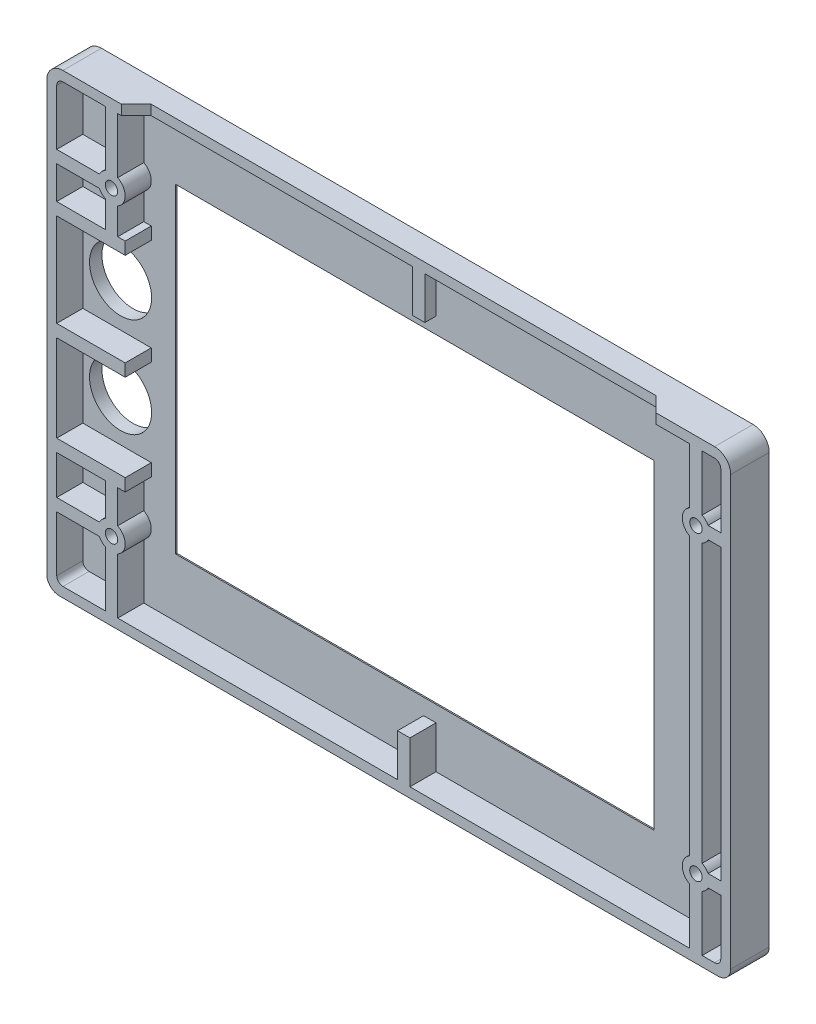
SolidWorks part; units mm, degrees
ref_plane "Спереди" through (0, 0, 0) normal (0, 0, 1) x (1, 0, 0)
ref_plane "Сверху" through (0, 0, 0) normal (0, 1, 0) x (1, 0, 0)
ref_plane "Справа" through (0, 0, 0) normal (1, 0, 0) x (0, 0, -1)
sketch "Эскиз1" plane through (0, 0, 0) normal (0, 0, 1) x (1, 0, 0)
  line L0 (-38.52, -25.78) -> (-38.52, 25.78)
  line L1 (38.52, -25.78) -> (-38.52, -25.78)
  line L2 (38.52, 25.78) -> (38.52, -25.78)
  line L3 (-38.52, 25.78) -> (38.52, 25.78)
  line L4 (50.46, 35.18) -> (50.46, 26.2296)
  line L5 (51.4196, 25.27) -> (53.46, 25.27)
  line L6 (53.46, 25.27) -> (53.46, 34.18)
  line L7 (52.46, 35.18) -> (50.46, 35.18)
  line L8 (50.46, 22.3104) -> (50.46, -22.3104)
  line L9 (51.4196, -23.27) -> (53.46, -23.27)
  line L10 (53.46, -23.27) -> (53.46, 23.27)
  line L11 (53.46, 23.27) -> (51.4196, 23.27)
  line L12 (50.46, -26.2296) -> (50.46, -35.18)
  line L13 (50.46, -35.18) -> (52.46, -35.18)
  line L14 (53.46, -34.18) -> (53.46, -25.27)
  line L15 (53.46, -25.27) -> (51.4196, -25.27)
  line L16 (-45.64, -22.3104) -> (-45.64, -17)
  line L17 (-45.64, -17) -> (-53.46, -17)
  line L18 (-53.46, -17) -> (-53.46, -23.27)
  line L19 (-53.46, -23.27) -> (-46.5996, -23.27)
  line L20 (1.41, -35.18) -> (1.41, -28.36)
  line L21 (1.41, -28.36) -> (3.41, -28.36)
  line L22 (3.41, -28.36) -> (3.41, -35.18)
  line L23 (3.41, -35.18) -> (48.46, -35.18)
  line L24 (48.46, -35.18) -> (48.46, -26.2296)
  line L25 (48.46, -22.3104) -> (48.46, 22.3104)
  line L26 (48.46, 26.2296) -> (48.46, 35.18)
  line L27 (48.46, 35.18) -> (3.41, 35.18)
  line L28 (3.41, 35.18) -> (3.41, 28.36)
  line L29 (3.41, 28.36) -> (1.41, 28.36)
  line L30 (1.41, 28.36) -> (1.41, 35.18)
  line L31 (1.41, 35.18) -> (-43.64, 35.18)
  line L32 (-43.64, 35.18) -> (-43.64, 26.2296)
  line L33 (-43.64, 22.3104) -> (-43.64, 18)
  line L34 (-43.64, 18) -> (-42.44, 18)
  line L35 (-42.44, 18) -> (-42.44, 16)
  line L36 (-42.44, 16) -> (-53.46, 16)
  line L37 (-53.46, 16) -> (-53.46, 1.0035)
  line L38 (-53.46, 1.0035) -> (-42.44, 1.0035)
  line L39 (-42.44, 1.0035) -> (-42.44, -0.9965)
  line L40 (-42.44, -0.9965) -> (-53.46, -0.9965)
  line L41 (-53.46, -0.9965) -> (-53.46, -15)
  line L42 (-53.46, -15) -> (-42.44, -15)
  line L43 (-42.44, -15) -> (-42.44, -17)
  line L44 (-42.44, -17) -> (-43.64, -17)
  line L45 (-43.64, -17) -> (-43.64, -22.3104)
  line L46 (-43.64, -26.2296) -> (-43.64, -35.18)
  line L47 (-43.64, -35.18) -> (1.41, -35.18)
  line L48 (-45.64, -35.18) -> (-45.64, -26.2296)
  line L49 (-46.5996, -25.27) -> (-53.46, -25.27)
  line L50 (-53.46, -25.27) -> (-53.46, -34.18)
  line L51 (-52.46, -35.18) -> (-45.64, -35.18)
  line L52 (-45.64, 18) -> (-45.64, 22.3104)
  line L53 (-46.5996, 23.27) -> (-53.46, 23.27)
  line L54 (-53.46, 23.27) -> (-53.46, 18)
  line L55 (-53.46, 18) -> (-45.64, 18)
  line L56 (-53.46, 25.27) -> (-46.5996, 25.27)
  line L57 (-45.64, 26.2296) -> (-45.64, 35.18)
  line L58 (-45.64, 35.18) -> (-52.46, 35.18)
  line L59 (-53.46, 34.18) -> (-53.46, 25.27)
  line L60 (55.06, -34.78) -> (55.06, 34.18)
  line L61 (40.66, 36.78) -> (43.06, 36.78)
  line L62 (40.66, 36.78) -> (-40.66, 36.78)
  line L63 (40.66, 35.18) -> (40.66, 36.78)
  line L64 (43.06, 35.18) -> (43.06, 36.78)
  line L65 (52.46, 36.78) -> (43.06, 36.78)
  line L66 (-53.06, -36.78) -> (53.06, -36.78)
  line L67 (-55.06, 34.18) -> (-55.06, -34.78)
  line L68 (-40.66, 36.78) -> (-40.66, 35.18)
  line L69 (-43.06, 35.18) -> (-43.06, 36.78)
  line L70 (-43.06, 36.78) -> (-40.66, 36.78)
  line L71 (-43.06, 36.78) -> (-52.46, 36.78)
  line L72 (9.4479, -31.9824) -> (8.7918, -31.9824)
  line L73 (10.3836, -30.0436) -> (10.3836, -34.7998)
  line L74 (9.4479, -30.6181) -> (9.4479, -31.9824)
  line L75 (9.4479, -32.6528) -> (9.4479, -34.2212)
  line L76 (8.6152, -32.6528) -> (9.4479, -32.6528)
  line L77 (4.3458, -34.8886) -> (5.2897, -34.8886)
  line L78 (5.2897, -34.8886) -> (5.2897, -29.961)
  line L79 (5.2897, -29.961) -> (4.3458, -29.961)
  line L80 (4.3458, -29.961) -> (4.3458, -34.8886)
  line L81 (2.357, -34.8886) -> (3.2805, -34.8886)
  line L82 (-0.0297, -34.2243) -> (0.7152, -34.2243)
  line L83 (-2.6022, -34.8886) -> (-1.6767, -34.8886)
  line L84 (-1.3889, -29.961) -> (-2.2012, -29.961)
  line L85 (2.8805, -29.961) -> (2.0805, -29.961)
  line L86 (-4.44, -32.5967) -> (-4.69, -32.5967)
  line L87 (-4.44, -31.9406) -> (-4.44, -32.5967)
  line L88 (-4.7594, -31.9406) -> (-4.44, -31.9406)
  line L89 (-3.5849, -30.2661) -> (-3.9104, -30.8457)
  line L90 (-3.6441, -34.0518) -> (-3.4839, -34.7161)
  line L91 (-8.0523, -34.8886) -> (-11.4727, -34.8886)
  line L92 (-11.4727, -34.8886) -> (-11.4727, -34.211)
  line L93 (-11.4727, -34.211) -> (-9.0145, -34.211)
  line L94 (-7.9329, -30.4844) -> (-8.3553, -31.012)
  arc A0 (51.4196, 25.27) -> (50.46, 26.2296) centre (49.46, 24.27) ccw
  arc A1 (53.46, 34.18) -> (52.46, 35.18) centre (52.46, 34.18) ccw
  arc A2 (48.46, -22.3104) -> (48.46, -26.2296) centre (49.46, -24.27) ccw
  arc A3 (48.46, 26.2296) -> (48.46, 22.3104) centre (49.46, 24.27) ccw
  arc A4 (-43.64, 22.3104) -> (-43.64, 26.2296) centre (-44.64, 24.27) ccw
  arc A5 (-43.64, -26.2296) -> (-43.64, -22.3104) centre (-44.64, -24.27) ccw
  arc A6 (51.4196, -23.27) -> (50.46, -22.3104) centre (49.46, -24.27) ccw
  arc A7 (50.46, 22.3104) -> (51.4196, 23.27) centre (49.46, 24.27) ccw
  circle A8 centre (49.46, 24.27) radius 1
  arc A9 (52.46, -35.18) -> (53.46, -34.18) centre (52.46, -34.18) ccw
  arc A10 (50.46, -26.2296) -> (51.4196, -25.27) centre (49.46, -24.27) ccw
  circle A11 centre (49.46, -24.27) radius 1
  circle A12 centre (-44.64, -24.27) radius 1
  circle A13 centre (-47.385, -8) radius 5
  arc A14 (-45.64, -22.3104) -> (-46.5996, -23.27) centre (-44.64, -24.27) ccw
  arc A15 (-46.5996, -25.27) -> (-45.64, -26.2296) centre (-44.64, -24.27) ccw
  arc A16 (-53.46, -34.18) -> (-52.46, -35.18) centre (-52.46, -34.18) ccw
  arc A17 (-46.5996, 23.27) -> (-45.64, 22.3104) centre (-44.64, 24.27) ccw
  arc A18 (-45.64, 26.2296) -> (-46.5996, 25.27) centre (-44.64, 24.27) ccw
  arc A19 (-52.46, 35.18) -> (-53.46, 34.18) centre (-52.46, 34.18) ccw
  circle A20 centre (-44.64, 24.27) radius 1
  arc A21 (55.06, 34.18) -> (52.46, 36.78) centre (52.46, 34.18) ccw
  arc A22 (53.06, -36.78) -> (55.06, -34.78) centre (53.06, -34.78) ccw
  arc A23 (-55.06, -34.78) -> (-53.06, -36.78) centre (-53.06, -34.78) ccw
  arc A24 (-52.46, 36.78) -> (-55.06, 34.18) centre (-52.46, 34.18) ccw
  circle A25 centre (-47.385, 8) radius 5
  spline S0 degree 3 poles (8.8387, -30.6038) (8.8833, -30.6036) (8.9673, -30.6032) (9.0853, -30.6059) (9.1881, -30.6074) (9.2745, -30.6106) (9.3438, -30.6137) (9.3948, -30.6162) (9.4275, -30.6165) (9.4431, -30.6177) (9.4479, -30.6181) knots 0 0 0 0 0.21934 0.413593 0.581062 0.725143 0.83911 0.922894 0.976499 1 1 1 1
  spline S1 degree 3 poles (8.7918, -31.9824) (8.703, -31.9808) (8.5318, -31.9778) (8.3224, -31.9585) (8.1673, -31.9307) (8.0608, -31.9062) (7.9634, -31.873) (7.8743, -31.8348) (7.7941, -31.7893) (7.7221, -31.7393) (7.6618, -31.6806) (7.6079, -31.6186) (7.567, -31.5468) (7.537, -31.4674) (7.5197, -31.3791) (7.5174, -31.3175) (7.5163, -31.2855) knots 0 0 0 0 0.163347 0.314852 0.386023 0.452934 0.515643 0.575031 0.631053 0.684865 0.735751 0.78549 0.835382 0.886853 0.941078 1 1 1 1
  spline S2 degree 3 poles (7.5163, -31.2855) (7.5173, -31.2558) (7.5194, -31.1981) (7.5385, -31.1159) (7.5677, -31.0403) (7.612, -30.9738) (7.6659, -30.9129) (7.7295, -30.8575) (7.804, -30.8086) (7.888, -30.765) (7.981, -30.726) (8.0841, -30.694) (8.1957, -30.6651) (8.3586, -30.636) (8.5736, -30.6092) (8.7492, -30.6057) (8.8387, -30.6038) knots 0 0 0 0 0.05392 0.104621 0.152614 0.200464 0.24909 0.299926 0.35343 0.410679 0.471653 0.536572 0.606754 0.680971 0.837269 1 1 1 1
  spline S3 degree 3 poles (6.5499, -31.2375) (6.5503, -31.2702) (6.551, -31.3344) (6.5632, -31.4285) (6.58, -31.5187) (6.6048, -31.6051) (6.6363, -31.6873) (6.6743, -31.7662) (6.7201, -31.8401) (6.7893, -31.9319) (6.8856, -32.0339) (7.0163, -32.1333) (7.1586, -32.2105) (7.2615, -32.24) (7.3132, -32.2549) knots 0 0 0 0 0.071306 0.140095 0.206635 0.271494 0.335883 0.398637 0.462303 0.525409 0.649341 0.766942 0.882847 1 1 1 1
  spline S4 degree 3 poles (8.8846, -29.912) (8.8067, -29.9128) (8.6525, -29.9144) (8.424, -29.9264) (8.2016, -29.9485) (7.9858, -29.976) (7.7792, -30.0137) (7.5847, -30.0653) (7.4024, -30.1263) (7.2348, -30.2026) (7.0811, -30.288) (6.9451, -30.3875) (6.8276, -30.4998) (6.7277, -30.6234) (6.648, -30.7597) (6.5904, -30.9079) (6.5558, -31.0689) (6.5519, -31.1802) (6.5499, -31.2375) knots 0 0 0 0 0.077891 0.154178 0.22866 0.301383 0.371619 0.438435 0.502425 0.563614 0.622247 0.677955 0.731594 0.784335 0.836305 0.88885 0.942744 1 1 1 1
  spline S5 degree 3 poles (8.8846, -29.912) (8.9411, -29.9124) (9.0578, -29.9132) (9.2367, -29.9199) (9.4225, -29.9289) (9.6109, -29.9411) (9.7995, -29.9561) (9.9887, -29.9757) (10.1841, -30.001) (10.3154, -30.029) (10.3836, -30.0436) knots 0 0 0 0 0.112395 0.232298 0.356344 0.482533 0.608194 0.732756 0.861249 1 1 1 1
  spline S6 degree 3 poles (9.4479, -34.2212) (9.4476, -34.2212) (9.4338, -34.2216) (9.415, -34.224) (9.3881, -34.2254) (9.3714, -34.2263) knots 0.196755 0.196755 0.196755 0.196755 0.204403 0.505519 1 1 1 1
  spline S7 degree 3 poles (9.3714, -34.2263) (9.3357, -34.228) (9.2588, -34.2317) (9.1337, -34.2376) (8.9891, -34.2389) (8.8857, -34.2387) (8.8306, -34.2386) knots 0 0 0 0 0.198249 0.426644 0.694476 1 1 1 1
  spline S8 degree 3 poles (8.8306, -34.2386) (8.7237, -34.2369) (8.5167, -34.2337) (8.2634, -34.2103) (8.074, -34.1825) (7.9439, -34.1541) (7.8241, -34.118) (7.7132, -34.077) (7.6129, -34.027) (7.5227, -33.9689) (7.4453, -33.9005) (7.376, -33.8262) (7.3216, -33.7401) (7.281, -33.6446) (7.2588, -33.5378) (7.2556, -33.4638) (7.254, -33.4253) knots 0 0 0 0 0.161567 0.312905 0.384192 0.451081 0.513893 0.573309 0.629663 0.683159 0.73493 0.785547 0.836198 0.888066 0.941735 1 1 1 1
  spline S9 degree 3 poles (7.254, -33.4253) (7.2553, -33.3905) (7.2578, -33.3237) (7.2734, -33.2271) (7.3036, -33.1402) (7.3437, -33.0608) (7.3957, -32.9905) (7.4561, -32.9254) (7.53, -32.8714) (7.6121, -32.8213) (7.7058, -32.7802) (7.8092, -32.7445) (7.9232, -32.7149) (8.0471, -32.6924) (8.1795, -32.6737) (8.3192, -32.6625) (8.4651, -32.6533) (8.5645, -32.653) (8.6152, -32.6528) knots 0 0 0 0 0.059005 0.1135 0.165365 0.214695 0.263903 0.313328 0.36484 0.418717 0.476355 0.538084 0.604336 0.67603 0.75182 0.831238 0.913947 1 1 1 1
  spline S10 degree 3 poles (2.1643, -31.3785) (2.1695, -31.4485) (2.1846, -31.6569) (2.2076, -32.0116) (2.2354, -32.4511) (2.2627, -32.9123) (2.2892, -33.3905) (2.3138, -33.881) (2.336, -34.3814) (2.35, -34.7185) (2.357, -34.8886) knots 0.048777 0.048777 0.048777 0.048777 0.105755 0.218376 0.337335 0.463184 0.593427 0.726123 0.861826 1 1 1 1
  spline S11 degree 3 poles (0.7152, -34.2243) (0.7316, -34.1896) (0.7654, -34.1179) (0.8168, -34.0059) (0.8756, -33.8887) (0.9365, -33.7635) (1.0024, -33.6325) (1.0688, -33.4933) (1.1414, -33.3486) (1.2379, -33.145) (1.363, -32.8883) (1.523, -32.5878) (1.6796, -32.2946) (1.8056, -32.0564) (1.9019, -31.873) (1.9703, -31.7439) (2.0387, -31.6232) (2.0923, -31.5275) (2.1326, -31.4564) (2.1508, -31.4127) (2.1611, -31.3874) (2.1643, -31.3785) knots 0 0 0 0 0.034001 0.070298 0.109281 0.150287 0.193721 0.239316 0.287067 0.337251 0.439092 0.540278 0.639048 0.733898 0.779229 0.82268 0.863459 0.902218 0.920031 0.935833 0.944187 0.944187 0.944187 0.944187
  spline S12 degree 3 poles (-0.0297, -34.2243) (-0.046, -34.1896) (-0.0798, -34.1177) (-0.1329, -34.0065) (-0.1898, -33.8883) (-0.2513, -33.7636) (-0.3167, -33.6322) (-0.3847, -33.4936) (-0.4568, -33.3483) (-0.5548, -33.1448) (-0.6838, -32.8899) (-0.8396, -32.5863) (-0.9975, -32.2899) (-1.1245, -32.0457) (-1.2245, -31.8571) (-1.295, -31.724) (-1.3641, -31.5999) (-1.4189, -31.5027) (-1.4589, -31.431) (-1.4749, -31.3951) (-1.482, -31.3773) (-1.4826, -31.3758) knots 0.056566 0.056566 0.056566 0.056566 0.090499 0.126852 0.165626 0.206551 0.249898 0.295535 0.34319 0.393406 0.495447 0.596014 0.695386 0.792598 0.839592 0.884302 0.925936 0.96529 0.983067 0.998563 1 1 1 1
  spline S13 degree 3 poles (-1.6767, -34.8886) (-1.6696, -34.7185) (-1.6557, -34.3817) (-1.6334, -33.8814) (-1.609, -33.3912) (-1.5824, -32.9133) (-1.5549, -32.4528) (-1.5277, -32.0136) (-1.5031, -31.6574) (-1.4878, -31.4474) (-1.4826, -31.3758) knots 0 0 0 0 0.138171 0.273597 0.406566 0.536531 0.662102 0.781058 0.893696 0.951951 0.951951 0.951951 0.951951
  spline S14 degree 3 poles (-2.2012, -29.961) (-2.2443, -30.3612) (-2.3312, -31.1678) (-2.4392, -32.3895) (-2.5321, -33.6318) (-2.5787, -34.4674) (-2.6022, -34.8886) knots 0 0 0 0 0.244221 0.492231 0.74407 1 1 1 1
  spline S15 degree 3 poles (-1.3889, -29.961) (-1.3506, -30.0179) (-1.2719, -30.1348) (-1.1563, -30.3176) (-1.0373, -30.5103) (-0.8772, -30.7858) (-0.674, -31.1485) (-0.4367, -31.5996) (-0.2042, -32.056) (-0.0123, -32.4281) (0.126, -32.7152) (0.2145, -32.9151) (0.2867, -33.1027) (0.3246, -33.2251) (0.3427, -33.2834) knots 0 0 0 0 0.054878 0.112558 0.17283 0.235807 0.367222 0.504974 0.643062 0.776526 0.839498 0.897672 0.951178 1 1 1 1
  spline S16 degree 3 poles (0.3427, -33.2834) (0.3608, -33.2251) (0.3986, -33.1027) (0.4713, -32.9156) (0.5567, -32.7151) (0.6947, -32.4303) (0.8804, -32.0602) (1.1142, -31.6125) (1.3498, -31.1692) (1.5891, -30.7445) (1.8271, -30.3408) (1.997, -30.0861) (2.0805, -29.961) knots 0 0 0 0 0.04878 0.102241 0.160149 0.222705 0.354839 0.490754 0.625976 0.755591 0.879939 1 1 1 1
  spline S17 degree 3 poles (2.8805, -29.961) (2.9049, -30.1534) (2.9537, -30.539) (3.0172, -31.1217) (3.0712, -31.7142) (3.1238, -32.3189) (3.1704, -32.937) (3.2125, -33.569) (3.2495, -34.2207) (3.27, -34.6627) (3.2805, -34.8886) knots 0 0 0 0 0.11768 0.235785 0.355571 0.478591 0.603995 0.73159 0.862829 1 1 1 1
  spline S18 degree 3 poles (-4.7594, -31.9406) (-4.8227, -31.9389) (-4.9516, -31.9356) (-5.1121, -31.9145) (-5.239, -31.8877) (-5.3305, -31.8629) (-5.416, -31.8294) (-5.4977, -31.7927) (-5.5717, -31.7458) (-5.6413, -31.6949) (-5.7, -31.6329) (-5.7547, -31.5671) (-5.7979, -31.4906) (-5.8283, -31.405) (-5.8472, -31.3104) (-5.8492, -31.2444) (-5.8502, -31.21) knots 0 0 0 0 0.128599 0.261659 0.328043 0.3919 0.453991 0.514249 0.573485 0.631648 0.688797 0.746296 0.805071 0.866034 0.930111 1 1 1 1
  spline S19 degree 3 poles (-5.8502, -31.21) (-5.8496, -31.1817) (-5.8483, -31.1268) (-5.8346, -31.048) (-5.8136, -30.9753) (-5.7822, -30.9096) (-5.7444, -30.8496) (-5.7012, -30.7943) (-5.6508, -30.7457) (-5.5955, -30.7017) (-5.535, -30.6623) (-5.4686, -30.6302) (-5.3976, -30.6032) (-5.2952, -30.5766) (-5.1594, -30.5526) (-5.0479, -30.5494) (-4.991, -30.5477) knots 0 0 0 0 0.069224 0.134278 0.19516 0.254043 0.312059 0.368394 0.425536 0.483041 0.541504 0.60186 0.663286 0.727145 0.860677 1 1 1 1
  spline S20 degree 3 poles (-4.991, -30.5477) (-4.9369, -30.5485) (-4.8331, -30.55) (-4.6837, -30.5669) (-4.5469, -30.5929) (-4.3789, -30.6487) (-4.1685, -30.7341) (-3.9994, -30.8072) (-3.9104, -30.8457) knots 0 0 0 0 0.143407 0.274916 0.398142 0.511615 0.743135 1 1 1 1
  spline S21 degree 3 poles (-6.0808, -33.46) (-6.0796, -33.4211) (-6.0773, -33.346) (-6.0549, -33.2387) (-6.0209, -33.1398) (-5.9697, -33.0519) (-5.9079, -32.9729) (-5.8365, -32.9017) (-5.756, -32.8382) (-5.6649, -32.7843) (-5.5654, -32.7372) (-5.457, -32.6978) (-5.3397, -32.6648) (-5.1717, -32.6323) (-4.9542, -32.6031) (-4.7782, -32.5988) (-4.69, -32.5967) knots 0 0 0 0 0.063414 0.122322 0.178344 0.233299 0.287497 0.341676 0.397433 0.454469 0.514074 0.576784 0.642525 0.712758 0.856069 1 1 1 1
  spline S22 degree 3 poles (-4.8675, -34.2875) (-4.9206, -34.2872) (-5.0232, -34.2865) (-5.1706, -34.2747) (-5.3064, -34.258) (-5.4299, -34.2337) (-5.5418, -34.2026) (-5.6412, -34.1633) (-5.7301, -34.1196) (-5.8055, -34.0653) (-5.8699, -34.0055) (-5.9268, -33.9419) (-5.9748, -33.8735) (-6.0143, -33.8003) (-6.0438, -33.7219) (-6.065, -33.6388) (-6.0788, -33.5509) (-6.0802, -33.4906) (-6.0808, -33.46) knots 0 0 0 0 0.095454 0.184416 0.265837 0.341304 0.410631 0.474364 0.533463 0.588294 0.640682 0.691385 0.741454 0.790719 0.840484 0.891676 0.944886 1 1 1 1
  spline S23 degree 3 poles (-4.8675, -34.2875) (-4.8015, -34.2868) (-4.6743, -34.2852) (-4.4914, -34.2683) (-4.3236, -34.2431) (-4.126, -34.1931) (-3.9029, -34.1232) (-3.7275, -34.0748) (-3.6441, -34.0518) knots 0 0 0 0 0.158157 0.304619 0.439944 0.564077 0.792564 1 1 1 1
  spline S24 degree 3 poles (-3.4839, -34.7161) (-3.5214, -34.7331) (-3.6011, -34.7692) (-3.7343, -34.8131) (-3.8879, -34.8545) (-4.062, -34.8961) (-4.2545, -34.9346) (-4.46, -34.9659) (-4.6708, -34.9885) (-4.8127, -34.9913) (-4.8828, -34.9926) knots 0 0 0 0 0.086022 0.182972 0.292897 0.41867 0.557194 0.703264 0.853385 1 1 1 1
  spline S25 degree 3 poles (-4.8828, -34.9926) (-4.9713, -34.9915) (-5.1425, -34.9892) (-5.39, -34.9661) (-5.6194, -34.9306) (-5.8309, -34.8782) (-6.0247, -34.8127) (-6.2028, -34.7377) (-6.3636, -34.6499) (-6.5073, -34.5507) (-6.6333, -34.4415) (-6.7413, -34.3233) (-6.8324, -34.1976) (-6.9029, -34.0623) (-6.9563, -33.9211) (-6.9973, -33.7759) (-7.0195, -33.6256) (-7.0229, -33.5243) (-7.0247, -33.4732) knots 0 0 0 0 0.089962 0.17401 0.252482 0.325884 0.39523 0.460312 0.522228 0.581139 0.637527 0.691389 0.743699 0.794911 0.846042 0.896975 0.948044 1 1 1 1
  spline S26 degree 3 poles (-7.0247, -33.4732) (-7.0233, -33.4317) (-7.0207, -33.35) (-7.005, -33.2296) (-6.9744, -33.1152) (-6.935, -33.0052) (-6.8838, -32.9015) (-6.8279, -32.8011) (-6.761, -32.708) (-6.6895, -32.6191) (-6.6091, -32.5369) (-6.5217, -32.4617) (-6.4269, -32.3936) (-6.3271, -32.3351) (-6.2277, -32.2865) (-6.1352, -32.2461) (-6.0492, -32.2213) (-5.9942, -32.2129) (-5.9686, -32.2089) knots 0 0 0 0 0.06994 0.137555 0.2038 0.269009 0.333802 0.39843 0.462131 0.526429 0.590405 0.655367 0.720198 0.78668 0.849929 0.906394 0.956416 1 1 1 1
  spline S27 degree 3 poles (-5.9686, -32.2089) (-6.0196, -32.1923) (-6.1231, -32.1585) (-6.2678, -32.0749) (-6.4056, -31.9685) (-6.5121, -31.862) (-6.5918, -31.768) (-6.6429, -31.6915) (-6.6869, -31.6127) (-6.7243, -31.5312) (-6.7515, -31.4461) (-6.7709, -31.3583) (-6.7837, -31.2678) (-6.7852, -31.2063) (-6.7859, -31.1753) knots 0 0 0 0 0.114054 0.231061 0.353418 0.483956 0.550788 0.615443 0.67929 0.7428 0.805987 0.869042 0.934057 1 1 1 1
  spline S28 degree 3 poles (-6.7859, -31.1753) (-6.785, -31.131) (-6.7831, -31.0432) (-6.7612, -30.9138) (-6.7289, -30.7875) (-6.6828, -30.665) (-6.6242, -30.5472) (-6.5493, -30.4371) (-6.4612, -30.3336) (-6.3585, -30.2374) (-6.2417, -30.1491) (-6.1092, -30.0713) (-5.9614, -30.0056) (-5.7996, -29.9494) (-5.6232, -29.9045) (-5.4325, -29.8724) (-5.2275, -29.8527) (-5.0863, -29.8508) (-5.0135, -29.8497) knots 0 0 0 0 0.05332 0.105591 0.157665 0.210174 0.262946 0.315787 0.370138 0.426369 0.484878 0.546222 0.610954 0.6795 0.752241 0.829972 0.912285 1 1 1 1
  spline S29 degree 3 poles (-5.0135, -29.8497) (-4.9395, -29.8516) (-4.7927, -29.8552) (-4.5781, -29.8879) (-4.3754, -29.9314) (-4.1881, -29.9823) (-4.0174, -30.0393) (-3.8617, -30.104) (-3.7172, -30.1775) (-3.6289, -30.2366) (-3.5849, -30.2661) knots 0 0 0 0 0.147019 0.291928 0.431041 0.559433 0.678001 0.788734 0.894679 1 1 1 1
  spline S30 degree 3 poles (-8.0523, -34.8886) (-8.0471, -34.8597) (-8.0384, -34.8117) (-8.032, -34.7489) (-8.033, -34.7028) (-8.0329, -34.6763) (-8.0329, -34.6641) knots 0 0 0 0 0.389156 0.647639 0.837372 1 1 1 1
  spline S31 degree 3 poles (-9.0145, -34.211) (-9.0161, -34.2003) (-9.02, -34.1737) (-9.0429, -34.1299) (-9.0736, -34.0721) (-9.1351, -33.9754) (-9.2285, -33.8431) (-9.3622, -33.6846) (-9.5109, -33.5278) (-9.6665, -33.3764) (-9.8197, -33.2379) (-9.9183, -33.1488) (-9.9645, -33.1069) knots 0 0 0 0 0.021915 0.054543 0.099576 0.156004 0.28792 0.429836 0.578605 0.728794 0.872731 1 1 1 1
  spline S32 degree 3 poles (-9.388, -32.5804) (-9.3098, -32.6515) (-9.151, -32.796) (-8.9109, -33.0129) (-8.6807, -33.2425) (-8.5065, -33.4478) (-8.382, -33.6201) (-8.2963, -33.753) (-8.2215, -33.8918) (-8.1543, -34.0346) (-8.0994, -34.183) (-8.0605, -34.3379) (-8.038, -34.4991) (-8.0346, -34.6086) (-8.0329, -34.6641) knots 0 0 0 0 0.123482 0.250869 0.377863 0.503065 0.564821 0.626105 0.687624 0.748955 0.810296 0.872165 0.935156 1 1 1 1
  spline S33 degree 3 poles (-9.4931, -30.5548) (-9.4306, -30.5568) (-9.3088, -30.5607) (-9.1353, -30.6011) (-8.978, -30.6552) (-8.8358, -30.718) (-8.7069, -30.7879) (-8.5939, -30.8717) (-8.4816, -30.9541) (-8.3976, -30.9926) (-8.3553, -31.012) knots 0 0 0 0 0.150082 0.29246 0.426517 0.549992 0.666122 0.778285 0.888375 1 1 1 1
  spline S34 degree 3 poles (-9.4931, -30.5548) (-9.5497, -30.5566) (-9.6605, -30.5599) (-9.7953, -30.588) (-9.8965, -30.6184) (-9.9665, -30.6484) (-10.0313, -30.6841) (-10.0905, -30.7263) (-10.1452, -30.7731) (-10.1931, -30.8265) (-10.2352, -30.885) (-10.2715, -30.9492) (-10.3011, -31.0196) (-10.3229, -31.0973) (-10.3348, -31.1824) (-10.3362, -31.2416) (-10.337, -31.2722) knots 0 0 0 0 0.135399 0.264894 0.327986 0.388175 0.446853 0.504682 0.56182 0.618888 0.676055 0.734022 0.79496 0.858372 0.926652 1 1 1 1
  spline S35 degree 3 poles (-9.388, -32.5804) (-9.4501, -32.5261) (-9.5717, -32.4198) (-9.7479, -32.2605) (-9.9083, -32.1019) (-10.0513, -31.9437) (-10.1705, -31.7832) (-10.2493, -31.6444) (-10.2956, -31.5317) (-10.3188, -31.4463) (-10.3339, -31.3598) (-10.336, -31.3015) (-10.337, -31.2722) knots 0 0 0 0 0.148632 0.291468 0.428085 0.555373 0.675595 0.787891 0.842105 0.894931 0.947163 1 1 1 1
  spline S36 degree 3 poles (-11.2962, -31.2508) (-11.2948, -31.292) (-11.292, -31.3747) (-11.2699, -31.4982) (-11.2325, -31.62) (-11.1821, -31.7402) (-11.1207, -31.8588) (-11.0481, -31.9749) (-10.9693, -32.0919) (-10.8459, -32.2463) (-10.6732, -32.4413) (-10.4436, -32.6681) (-10.204, -32.89) (-10.0432, -33.0356) (-9.9645, -33.1069) knots 0 0 0 0 0.052684 0.105639 0.159681 0.21522 0.271989 0.330139 0.390182 0.452096 0.582665 0.722824 0.864298 1 1 1 1
  spline S37 degree 3 poles (-11.2962, -31.2508) (-11.2949, -31.1983) (-11.2923, -31.0957) (-11.2704, -30.9458) (-11.2348, -30.8047) (-11.1857, -30.6711) (-11.1209, -30.5468) (-11.0433, -30.4298) (-10.9487, -30.3238) (-10.8429, -30.2241) (-10.7218, -30.135) (-10.5863, -30.0584) (-10.4368, -29.9945) (-10.2741, -29.9395) (-10.096, -29.9002) (-9.9048, -29.8704) (-9.6995, -29.8532) (-9.5581, -29.8509) (-9.4849, -29.8497) knots 0 0 0 0 0.060615 0.118612 0.174591 0.228711 0.282699 0.336244 0.390581 0.446499 0.504143 0.563838 0.626 0.6919 0.762101 0.836507 0.91543 1 1 1 1
  spline S38 degree 3 poles (-7.9329, -30.4844) (-7.9663, -30.4471) (-8.0371, -30.3678) (-8.1705, -30.2625) (-8.3296, -30.1617) (-8.5139, -30.0652) (-8.7245, -29.9798) (-8.9172, -29.922) (-9.0823, -29.8833) (-9.2131, -29.8651) (-9.3476, -29.8519) (-9.4386, -29.8505) (-9.4849, -29.8497) knots 0 0 0 0 0.087147 0.184828 0.294576 0.414848 0.54661 0.689569 0.764861 0.841503 0.919416 1 1 1 1
sketch "Эскиз2" plane through (0, 0, 0) normal (0, 0, 1) x (1, 0, 0)
  line L0 (-55.06, 34.18) -> (-55.06, -34.78) construction
  line L1 (-43.06, 36.78) -> (-52.46, 36.78) construction
  line L2 (-43.06, 36.78) -> (-40.66, 36.78) construction
  line L3 (38.52, 25.78) -> (38.52, -25.78) construction
  line L4 (-38.52, 25.78) -> (38.52, 25.78) construction
  line L5 (55.06, -34.78) -> (55.06, 34.18) construction
  line L6 (52.46, 36.78) -> (43.06, 36.78) construction
  line L7 (40.66, 36.78) -> (43.06, 36.78) construction
  line L8 (40.66, 36.78) -> (-40.66, 36.78) construction
  line L9 (-55.06, 34.18) -> (-55.06, -34.78)
  line L10 (-43.06, 36.78) -> (-52.46, 36.78)
  line L11 (-43.06, 36.78) -> (-40.66, 36.78)
  line L12 (38.52, 25.78) -> (38.52, -25.78)
  line L13 (-38.52, 25.78) -> (38.52, 25.78)
  line L14 (55.06, -34.78) -> (55.06, 34.18)
  line L15 (52.46, 36.78) -> (43.06, 36.78)
  line L16 (40.66, 36.78) -> (43.06, 36.78)
  line L17 (40.66, 36.78) -> (-40.66, 36.78)
  line L18 (38.52, -25.78) -> (-38.52, -25.78) construction
  line L19 (-38.52, -25.78) -> (-38.52, 25.78) construction
  line L20 (38.52, -25.78) -> (-38.52, -25.78)
  line L21 (-38.52, -25.78) -> (-38.52, 25.78)
  line L22 (-53.06, -36.78) -> (53.06, -36.78) construction
  line L23 (-53.06, -36.78) -> (53.06, -36.78)
  arc A0 (-52.46, 36.78) -> (-55.06, 34.18) centre (-52.46, 34.18) ccw construction
  arc A1 (55.06, 34.18) -> (52.46, 36.78) centre (52.46, 34.18) ccw construction
  arc A2 (-52.46, 36.78) -> (-55.06, 34.18) centre (-52.46, 34.18) ccw
  arc A3 (55.06, 34.18) -> (52.46, 36.78) centre (52.46, 34.18) ccw
  circle A4 centre (-47.385, 8) radius 5 construction
  circle A5 centre (-47.385, 8) radius 5
  circle A6 centre (-47.385, -8) radius 5 construction
  circle A7 centre (-47.385, -8) radius 5
  arc A8 (53.06, -36.78) -> (55.06, -34.78) centre (53.06, -34.78) ccw construction
  arc A9 (-55.06, -34.78) -> (-53.06, -36.78) centre (-53.06, -34.78) ccw construction
  arc A10 (53.06, -36.78) -> (55.06, -34.78) centre (53.06, -34.78) ccw
  arc A11 (-55.06, -34.78) -> (-53.06, -36.78) centre (-53.06, -34.78) ccw
extrude "Бобышка-Вытянуть1" add sketch "Эскиз2" along normal blind 2
sketch "Эскиз3" plane through (0, 0, 2) normal (0, 0, 1) x (1, 0, 0)
  line L0 (-55.06, 34.18) -> (-55.06, -34.78) construction
  line L1 (-45.64, 35.18) -> (-52.46, 35.18) construction
  line L2 (-45.64, 26.2296) -> (-45.64, 35.18) construction
  line L3 (-45.64, 18) -> (-45.64, 22.3104) construction
  line L4 (-42.44, 16) -> (-53.46, 16) construction
  line L5 (-42.44, 18) -> (-42.44, 16) construction
  line L6 (-43.64, 22.3104) -> (-43.64, 18) construction
  line L7 (-43.64, 35.18) -> (-43.64, 26.2296) construction
  line L8 (1.41, 35.18) -> (-43.64, 35.18) construction
  line L9 (40.66, 36.78) -> (-40.66, 36.78) construction
  line L10 (-43.06, 36.78) -> (-40.66, 36.78) construction
  line L11 (-43.06, 36.78) -> (-52.46, 36.78) construction
  line L12 (-55.06, 34.18) -> (-55.06, -34.78)
  line L13 (-45.64, 35.18) -> (-52.46, 35.18)
  line L14 (-45.64, 26.2296) -> (-45.64, 35.18)
  line L15 (-45.64, 18) -> (-45.64, 22.3104)
  line L16 (-42.44, 16) -> (-53.46, 16)
  line L17 (-42.44, 18) -> (-42.44, 16)
  line L18 (-43.64, 22.3104) -> (-43.64, 18)
  line L19 (-43.64, 35.18) -> (-43.64, 26.2296)
  line L20 (1.41, 35.18) -> (-43.64, 35.18)
  line L21 (40.66, 36.78) -> (-40.66, 36.78)
  line L22 (-43.06, 36.78) -> (-40.66, 36.78)
  line L23 (-43.06, 36.78) -> (-52.46, 36.78)
  line L24 (-53.46, 25.27) -> (-46.5996, 25.27) construction
  line L25 (-53.46, 34.18) -> (-53.46, 25.27) construction
  line L26 (-53.46, 25.27) -> (-46.5996, 25.27)
  line L27 (-53.46, 34.18) -> (-53.46, 25.27)
  line L28 (-53.46, 18) -> (-45.64, 18) construction
  line L29 (-53.46, 23.27) -> (-53.46, 18) construction
  line L30 (-46.5996, 23.27) -> (-53.46, 23.27) construction
  line L31 (-53.46, 18) -> (-45.64, 18)
  line L32 (-53.46, 23.27) -> (-53.46, 18)
  line L33 (-46.5996, 23.27) -> (-53.46, 23.27)
  line L34 (-53.46, 16) -> (-53.46, 1.0035) construction
  line L35 (-43.64, 18) -> (-42.44, 18) construction
  line L36 (-53.46, 16) -> (-53.46, 1.0035)
  line L37 (-43.64, 18) -> (-42.44, 18)
  line L38 (-43.64, -17) -> (-43.64, -22.3104) construction
  line L39 (-42.44, -15) -> (-42.44, -17) construction
  line L40 (-53.46, -15) -> (-42.44, -15) construction
  line L41 (-53.46, -0.9965) -> (-53.46, -15) construction
  line L42 (-42.44, 1.0035) -> (-42.44, -0.9965) construction
  line L43 (-42.44, -0.9965) -> (-53.46, -0.9965) construction
  line L44 (-53.46, 1.0035) -> (-42.44, 1.0035) construction
  line L45 (-43.64, -17) -> (-43.64, -22.3104)
  line L46 (-42.44, -15) -> (-42.44, -17)
  line L47 (-53.46, -15) -> (-42.44, -15)
  line L48 (-53.46, -0.9965) -> (-53.46, -15)
  line L49 (-42.44, 1.0035) -> (-42.44, -0.9965)
  line L50 (-42.44, -0.9965) -> (-53.46, -0.9965)
  line L51 (-53.46, 1.0035) -> (-42.44, 1.0035)
  line L52 (-53.46, -17) -> (-53.46, -23.27) construction
  line L53 (-45.64, -22.3104) -> (-45.64, -17) construction
  line L54 (-45.64, -17) -> (-53.46, -17) construction
  line L55 (-42.44, -17) -> (-43.64, -17) construction
  line L56 (-53.46, -17) -> (-53.46, -23.27)
  line L57 (-45.64, -22.3104) -> (-45.64, -17)
  line L58 (-45.64, -17) -> (-53.46, -17)
  line L59 (-42.44, -17) -> (-43.64, -17)
  line L60 (-43.64, -35.18) -> (1.41, -35.18) construction
  line L61 (-43.64, -26.2296) -> (-43.64, -35.18) construction
  line L62 (-45.64, -35.18) -> (-45.64, -26.2296) construction
  line L63 (-52.46, -35.18) -> (-45.64, -35.18) construction
  line L64 (-53.06, -36.78) -> (53.06, -36.78) construction
  line L65 (-53.46, -25.27) -> (-53.46, -34.18) construction
  line L66 (-46.5996, -25.27) -> (-53.46, -25.27) construction
  line L67 (-53.46, -23.27) -> (-46.5996, -23.27) construction
  line L68 (-43.64, -35.18) -> (1.41, -35.18)
  line L69 (-43.64, -26.2296) -> (-43.64, -35.18)
  line L70 (-45.64, -35.18) -> (-45.64, -26.2296)
  line L71 (-52.46, -35.18) -> (-45.64, -35.18)
  line L72 (-53.06, -36.78) -> (53.06, -36.78)
  line L73 (-53.46, -25.27) -> (-53.46, -34.18)
  line L74 (-46.5996, -25.27) -> (-53.46, -25.27)
  line L75 (-53.46, -23.27) -> (-46.5996, -23.27)
  line L76 (3.41, -35.18) -> (48.46, -35.18) construction
  line L77 (3.41, -28.36) -> (3.41, -35.18) construction
  line L78 (1.41, -28.36) -> (3.41, -28.36) construction
  line L79 (1.41, -35.18) -> (1.41, -28.36) construction
  line L80 (3.41, -35.18) -> (48.46, -35.18)
  line L81 (3.41, -28.36) -> (3.41, -35.18)
  line L82 (1.41, -28.36) -> (3.41, -28.36)
  line L83 (1.41, -35.18) -> (1.41, -28.36)
  line L84 (53.46, -23.27) -> (53.46, 23.27) construction
  line L85 (51.4196, -23.27) -> (53.46, -23.27) construction
  line L86 (53.46, -25.27) -> (51.4196, -25.27) construction
  line L87 (48.46, -35.18) -> (48.46, -26.2296) construction
  line L88 (50.46, -26.2296) -> (50.46, -35.18) construction
  line L89 (50.46, -35.18) -> (52.46, -35.18) construction
  line L90 (53.46, -34.18) -> (53.46, -25.27) construction
  line L91 (55.06, -34.78) -> (55.06, 34.18) construction
  line L92 (53.46, -23.27) -> (53.46, 23.27)
  line L93 (51.4196, -23.27) -> (53.46, -23.27)
  line L94 (53.46, -25.27) -> (51.4196, -25.27)
  line L95 (48.46, -35.18) -> (48.46, -26.2296)
  line L96 (50.46, -26.2296) -> (50.46, -35.18)
  line L97 (50.46, -35.18) -> (52.46, -35.18)
  line L98 (53.46, -34.18) -> (53.46, -25.27)
  line L99 (55.06, -34.78) -> (55.06, 34.18)
  line L100 (48.46, -22.3104) -> (48.46, 22.3104) construction
  line L101 (50.46, 22.3104) -> (50.46, -22.3104) construction
  line L102 (48.46, -22.3104) -> (48.46, 22.3104)
  line L103 (50.46, 22.3104) -> (50.46, -22.3104)
  line L104 (3.41, 28.36) -> (1.41, 28.36) construction
  line L105 (48.46, 35.18) -> (3.41, 35.18) construction
  line L106 (3.41, 35.18) -> (3.41, 28.36) construction
  line L107 (1.41, 28.36) -> (1.41, 35.18) construction
  line L108 (3.41, 28.36) -> (1.41, 28.36)
  line L109 (48.46, 35.18) -> (3.41, 35.18)
  line L110 (3.41, 35.18) -> (3.41, 28.36)
  line L111 (1.41, 28.36) -> (1.41, 35.18)
  line L112 (53.46, 23.27) -> (51.4196, 23.27) construction
  line L113 (48.46, 26.2296) -> (48.46, 35.18) construction
  line L114 (50.46, 35.18) -> (50.46, 26.2296) construction
  line L115 (51.4196, 25.27) -> (53.46, 25.27) construction
  line L116 (53.46, 25.27) -> (53.46, 34.18) construction
  line L117 (53.46, 23.27) -> (51.4196, 23.27)
  line L118 (48.46, 26.2296) -> (48.46, 35.18)
  line L119 (50.46, 35.18) -> (50.46, 26.2296)
  line L120 (51.4196, 25.27) -> (53.46, 25.27)
  line L121 (53.46, 25.27) -> (53.46, 34.18)
  line L122 (52.46, 35.18) -> (50.46, 35.18) construction
  line L123 (52.46, 36.78) -> (43.06, 36.78) construction
  line L124 (40.66, 36.78) -> (43.06, 36.78) construction
  line L125 (52.46, 35.18) -> (50.46, 35.18)
  line L126 (52.46, 36.78) -> (43.06, 36.78)
  line L127 (40.66, 36.78) -> (43.06, 36.78)
  arc A0 (-52.46, 36.78) -> (-55.06, 34.18) centre (-52.46, 34.18) ccw construction
  arc A1 (-45.64, 26.2296) -> (-46.5996, 25.27) centre (-44.64, 24.27) ccw construction
  arc A2 (-46.5996, 23.27) -> (-45.64, 22.3104) centre (-44.64, 24.27) ccw construction
  circle A3 centre (-44.64, 24.27) radius 1 construction
  arc A4 (-43.64, 22.3104) -> (-43.64, 26.2296) centre (-44.64, 24.27) ccw construction
  arc A5 (-52.46, 36.78) -> (-55.06, 34.18) centre (-52.46, 34.18) ccw
  arc A6 (-45.64, 26.2296) -> (-46.5996, 25.27) centre (-44.64, 24.27) ccw
  arc A7 (-46.5996, 23.27) -> (-45.64, 22.3104) centre (-44.64, 24.27) ccw
  circle A8 centre (-44.64, 24.27) radius 1
  arc A9 (-43.64, 22.3104) -> (-43.64, 26.2296) centre (-44.64, 24.27) ccw
  arc A10 (-52.46, 35.18) -> (-53.46, 34.18) centre (-52.46, 34.18) ccw construction
  arc A11 (-52.46, 35.18) -> (-53.46, 34.18) centre (-52.46, 34.18) ccw
  arc A12 (-43.64, -26.2296) -> (-43.64, -22.3104) centre (-44.64, -24.27) ccw construction
  arc A13 (-45.64, -22.3104) -> (-46.5996, -23.27) centre (-44.64, -24.27) ccw construction
  arc A14 (-43.64, -26.2296) -> (-43.64, -22.3104) centre (-44.64, -24.27) ccw
  arc A15 (-45.64, -22.3104) -> (-46.5996, -23.27) centre (-44.64, -24.27) ccw
  arc A16 (-46.5996, -25.27) -> (-45.64, -26.2296) centre (-44.64, -24.27) ccw construction
  arc A17 (-55.06, -34.78) -> (-53.06, -36.78) centre (-53.06, -34.78) ccw construction
  arc A18 (-53.46, -34.18) -> (-52.46, -35.18) centre (-52.46, -34.18) ccw construction
  circle A19 centre (-44.64, -24.27) radius 1 construction
  arc A20 (-46.5996, -25.27) -> (-45.64, -26.2296) centre (-44.64, -24.27) ccw
  arc A21 (-55.06, -34.78) -> (-53.06, -36.78) centre (-53.06, -34.78) ccw
  arc A22 (-53.46, -34.18) -> (-52.46, -35.18) centre (-52.46, -34.18) ccw
  circle A23 centre (-44.64, -24.27) radius 1
  arc A24 (50.46, -26.2296) -> (51.4196, -25.27) centre (49.46, -24.27) ccw construction
  circle A25 centre (49.46, -24.27) radius 1 construction
  arc A26 (48.46, -22.3104) -> (48.46, -26.2296) centre (49.46, -24.27) ccw construction
  arc A27 (52.46, -35.18) -> (53.46, -34.18) centre (52.46, -34.18) ccw construction
  arc A28 (53.06, -36.78) -> (55.06, -34.78) centre (53.06, -34.78) ccw construction
  arc A29 (50.46, -26.2296) -> (51.4196, -25.27) centre (49.46, -24.27) ccw
  circle A30 centre (49.46, -24.27) radius 1
  arc A31 (48.46, -22.3104) -> (48.46, -26.2296) centre (49.46, -24.27) ccw
  arc A32 (52.46, -35.18) -> (53.46, -34.18) centre (52.46, -34.18) ccw
  arc A33 (53.06, -36.78) -> (55.06, -34.78) centre (53.06, -34.78) ccw
  arc A34 (51.4196, -23.27) -> (50.46, -22.3104) centre (49.46, -24.27) ccw construction
  arc A35 (51.4196, -23.27) -> (50.46, -22.3104) centre (49.46, -24.27) ccw
  arc A36 (50.46, 22.3104) -> (51.4196, 23.27) centre (49.46, 24.27) ccw construction
  circle A37 centre (49.46, 24.27) radius 1 construction
  arc A38 (48.46, 26.2296) -> (48.46, 22.3104) centre (49.46, 24.27) ccw construction
  arc A39 (51.4196, 25.27) -> (50.46, 26.2296) centre (49.46, 24.27) ccw construction
  arc A40 (50.46, 22.3104) -> (51.4196, 23.27) centre (49.46, 24.27) ccw
  circle A41 centre (49.46, 24.27) radius 1
  arc A42 (48.46, 26.2296) -> (48.46, 22.3104) centre (49.46, 24.27) ccw
  arc A43 (51.4196, 25.27) -> (50.46, 26.2296) centre (49.46, 24.27) ccw
  arc A44 (53.46, 34.18) -> (52.46, 35.18) centre (52.46, 34.18) ccw construction
  arc A45 (55.06, 34.18) -> (52.46, 36.78) centre (52.46, 34.18) ccw construction
  arc A46 (53.46, 34.18) -> (52.46, 35.18) centre (52.46, 34.18) ccw
  arc A47 (55.06, 34.18) -> (52.46, 36.78) centre (52.46, 34.18) ccw
extrude "Бобышка-Вытянуть2" add sketch "Эскиз3" along normal blind 4.2
sketch "Эскиз4" plane through (0, 0, 6.2) normal (0, 0, 1) x (1, 0, 0)
  line L0 (43.06, 35.18) -> (43.06, 36.78) construction
  line L1 (40.66, 36.78) -> (43.06, 36.78) construction
  line L2 (40.66, 36.78) -> (-40.66, 36.78) construction
  line L3 (-43.06, 36.78) -> (-40.66, 36.78) construction
  line L4 (-43.06, 35.18) -> (-43.06, 36.78) construction
  line L5 (43.06, 35.18) -> (43.06, 36.78)
  line L6 (40.66, 36.78) -> (43.06, 36.78)
  line L7 (40.66, 36.78) -> (-40.66, 36.78)
  line L8 (-43.06, 36.78) -> (-40.66, 36.78)
  line L9 (-43.06, 35.18) -> (-43.06, 36.78)
  line L10 (3.41, 28.36) -> (1.41, 28.36) construction
  line L11 (1.41, 28.36) -> (1.41, 35.18) construction
  line L12 (3.41, 35.18) -> (3.41, 28.36) construction
  line L13 (3.41, 28.36) -> (1.41, 28.36)
  line L14 (1.41, 28.36) -> (1.41, 35.18)
  line L15 (3.41, 35.18) -> (3.41, 28.36)
  line L16 (1.41, 35.18) -> (-43.06, 35.18)
  line L17 (3.41, 35.18) -> (43.06, 35.18)
extrude "Вырез-Вытянуть1" cut sketch "Эскиз4" against normal blind 2.4
chamfer "Фаска1" distance 2.4 angle 45 2 edges at (43.06, 35.98, 3.8) (-43.06, 35.98, 3.8)
chamfer "Фаска2" distance 1.8 angle 45 4 edges at (0, -25.78, 0) (38.52, 0, 0) (0, 25.78, 0) (-38.52, 0, 0)
